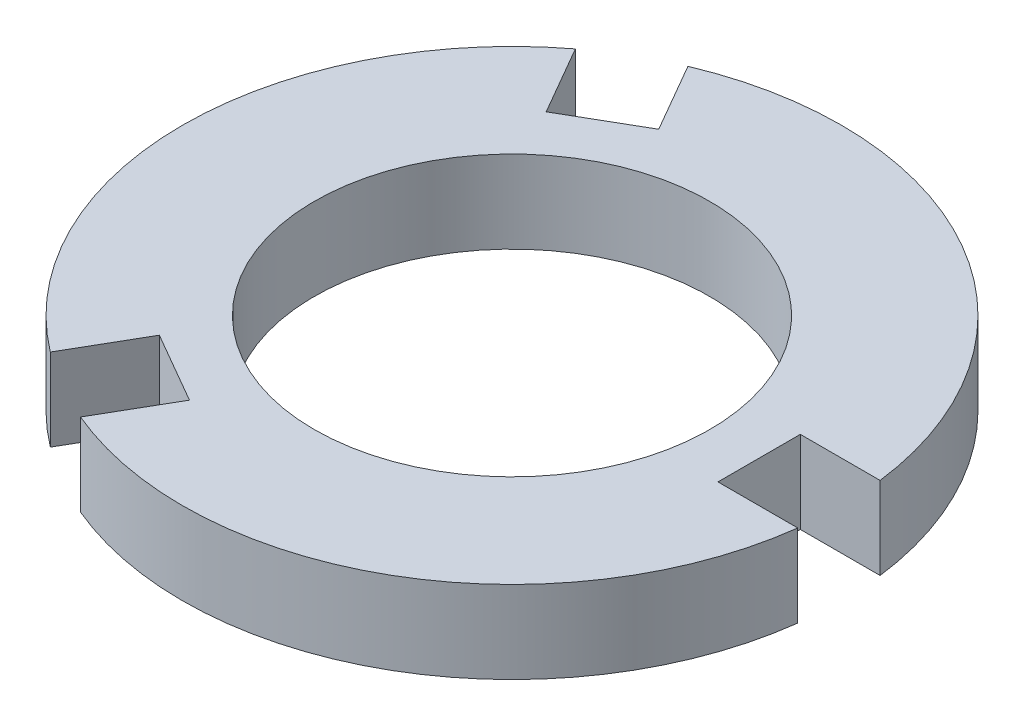
SolidWorks part; units mm, degrees
note: '?' marks a value the reader was unsure of.
ref_plane "Front Plane" through (0, 0, 0) normal (0, 0, 1) x (1, 0, 0)
ref_plane "Top Plane" through (0, 0, 0) normal (0, 1, 0) x (1, 0, 0)
ref_plane "Right Plane" through (0, 0, 0) normal (1, 0, 0) x (0, 0, -1)
sketch "Sketch1" plane through (0, 0, 0) normal (0, 1, 0) x (1, 0, 0)
  circle A0 centre (0, 0) radius 100
  circle A1 centre (0, 0) radius 60
  dimension "D1" = 40
  dimension "D2" = 120
extrude "Boss-Extrude1" add sketch "Sketch1" along normal blind 25
sketch "Sketch2" plane through (0, 25, 0) normal (0, 1, 0) x (1, 0, 0)
  line L0 (0, 0) -> (100, 0) construction
  line L6 (75, 12.5) -> (100, 12.5)
  line L7 (75, 12.5) -> (75, -12.5)
  line L8 (75, -12.5) -> (100, -12.5)
  line L9 (100, 12.5) -> (100, -12.5)
  circle A2 centre (0, 0) radius 100 construction
  point P1 (100, 0)
  dimension "D1" = 25
  dimension "D2" = 25
other "Pen Sketch1" parameters "D1"=25, "D2"=25
extrude "Cut-Extrude1" cut sketch "Sketch2" against normal through all
ref_axis "Axis1" through (0, 0, 0) along (0, 1, 0)?
pattern_circular "CirPattern1" count 3 every 120 about axis through (0, 0, 0) along (0, 1, 0) of "Cut-Extrude1"
ref_axis "Axis3" through (0, 0, 0) along (1, 0, 0)?
